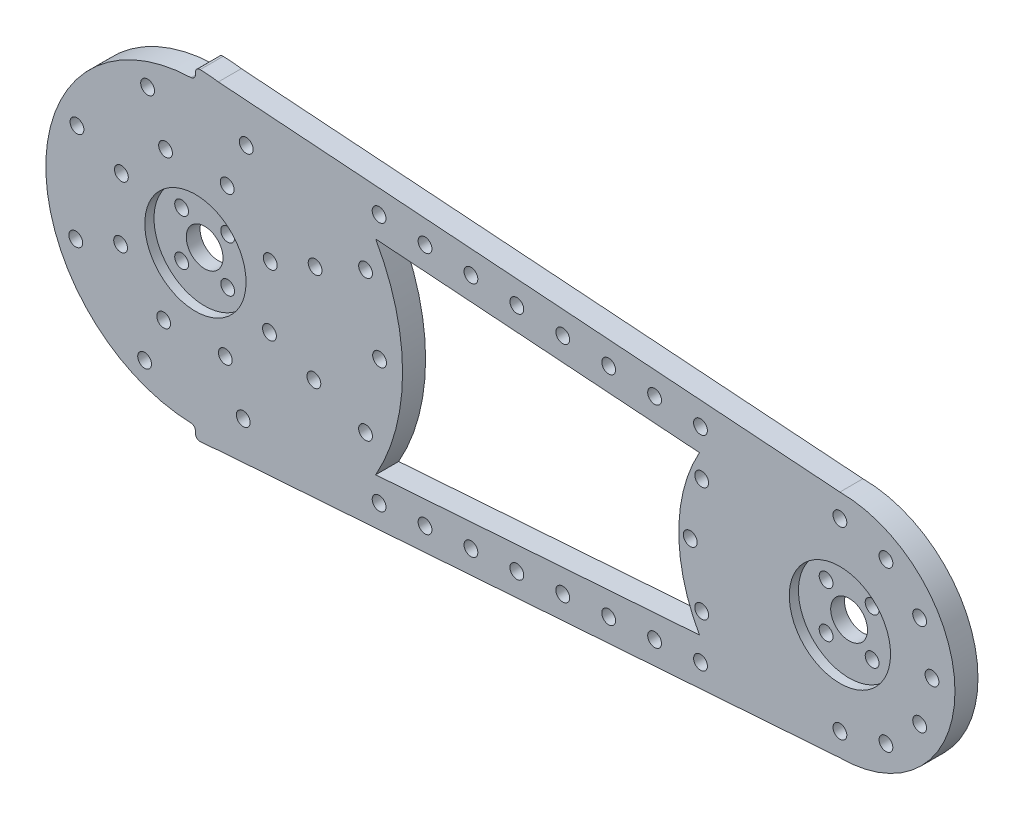
SolidWorks part; units mm, degrees
ref_plane "前视基准面" through (0, 0, 0) normal (0, 0, 1) x (1, 0, 0)
ref_plane "上视基准面" through (0, 0, 0) normal (0, 1, 0) x (1, 0, 0)
ref_plane "右视基准面" through (0, 0, 0) normal (1, 0, 0) x (0, 0, -1)
other "Configuration Table"
sketch "草图1" plane through (0, 0, 0) normal (0, 0, 1) x (1, 0, 0)
  line L0 (0, 0) -> (140, 0)
  line L1 (0, 35) -> (140, 25)
  line L2 (0, -35) -> (140, -25)
  circle A0 centre (0, 0) radius 35
  circle A1 centre (140, 0) radius 25
  dimension "D1" = 70
  dimension "D3" = 50
  dimension "D2" = 140
extrude "凸台-拉伸3" add sketch "草图1" along normal blind 5
sketch "草图4" plane through (0, 0, 5) normal (0, 0, 1) x (1, 0, 0)
  line L1 (-5, -5) -> (5, -5)
  line L2 (-5, -5) -> (-5, 5)
  line L3 (-5, 5) -> (5, 5)
  line L4 (5, -5) -> (5, 5)
  line L5 (-5, -5) -> (5, 5) construction
  line L6 (-5, 5) -> (5, -5) construction
  line L7 (135, -5) -> (145, -5)
  line L8 (135, -5) -> (135, 5)
  line L9 (135, 5) -> (145, 5)
  line L10 (145, -5) -> (145, 5)
  line L11 (135, -5) -> (145, 5) construction
  line L12 (135, 5) -> (145, -5) construction
  circle A0 centre (0, 0) radius 4
  circle A1 centre (-5, 5) radius 1.5
  circle A2 centre (5, 5) radius 1.5
  circle A3 centre (5, -5) radius 1.5
  circle A4 centre (-5, -5) radius 1.5
  circle A5 centre (140, 0) radius 4
  circle A6 centre (135, 5) radius 1.5
  circle A7 centre (145, 5) radius 1.5
  circle A8 centre (145, -5) radius 1.5
  circle A9 centre (135, -5) radius 1.5
  dimension "D1" = 8
  dimension "D4" = 3
  dimension "D6" = 8
  dimension "D9" = 3
  dimension "D2" = 10
  dimension "D3" = 10
  dimension "D7" = 10
  dimension "D8" = 10
  dimension "D5" = 4
  dimension "D10" = 4
extrude "切除-拉伸3" cut sketch "草图4" against normal blind 5 contours A5 | A0 | L2 A4 L1 | L1 A4 L2 | A6 | A9 | A8 | A7 | A1 | A2 | A3
sketch "草图5" plane through (0, 0, 5) normal (0, 0, 1) x (1, 0, 0)
  circle A0 centre (0, 0) radius 11
  circle A1 centre (140, 0) radius 11
  dimension "D1" = 22
  dimension "D2" = 22
extrude "切除-拉伸4" cut sketch "草图5" against normal blind 2
sketch "草图6" plane through (0, 0, 5) normal (0, 0, 1) x (1, 0, 0)
  circle A0 centre (0, 0) radius 30
  circle A1 centre (0, 30) radius 1.5
  circle A2 centre (15, 25.9808) radius 1.5
  circle A3 centre (25.9808, 15) radius 1.5
  circle A4 centre (30, 0) radius 1.5
  circle A5 centre (25.9808, -15) radius 1.5
  circle A6 centre (15, -25.9808) radius 1.5
  circle A7 centre (0, -30) radius 1.5
  circle A8 centre (-15, -25.9808) radius 1.5
  circle A9 centre (-25.9808, -15) radius 1.5
  circle A10 centre (-30, 0) radius 1.5
  circle A11 centre (-25.9808, 15) radius 1.5
  circle A12 centre (-15, 25.9808) radius 1.5
  circle A13 centre (140, 0) radius 20
  circle A14 centre (140, 20) radius 1.5
  circle A15 centre (150, 17.3205) radius 1.5
  circle A16 centre (157.3205, 10) radius 1.5
  circle A17 centre (160, 0) radius 1.5
  circle A18 centre (157.3205, -10) radius 1.5
  circle A19 centre (150, -17.3205) radius 1.5
  circle A20 centre (140, -20) radius 1.5
  circle A21 centre (130, -17.3205) radius 1.5
  circle A22 centre (122.6795, -10) radius 1.5
  circle A23 centre (120, 0) radius 1.5
  circle A24 centre (122.6795, 10) radius 1.5
  circle A25 centre (130, 17.3205) radius 1.5
  point P29 (0, 0)
  dimension "D1" = 60
  dimension "D2" = 3
  dimension "D4" = 40
  dimension "D5" = 3
  dimension "D3" = 12
  dimension "D6" = 12
extrude "切除-拉伸6" cut sketch "草图6" against normal through all contours A0 A12 | A11 | A1 | A2 | A3 | A4 | A5 | A6 | A7 | A8 | A9 | A10 | A25 | A14 | A15 | A16 | A17 | A18 | A19 | A20 | A21 | A22 | A23 | A24
sketch "草图8" plane through (0, 0, 5) normal (0, 0, 1) x (1, 0, 0)
  line L4 (-0.1715, -29.9995) -> (139.8316, -19.9993)
  line L5 (139.8316, 19.9993) -> (-0.1715, 29.9995)
  line L6 (-0.1715, -29.9995) -> (139.8316, -19.9993)
  line L7 (139.8316, 19.9993) -> (-0.1715, 29.9995)
  line L8 (-0.7125, 25.0254) -> (139.2875, 15.0254)
  line L9 (-0.7125, 25.0254) -> (139.2875, 15.0254)
  line L11 (-0.7125, -25.0254) -> (139.2875, -15.0254)
  line L12 (-0.7125, -25.0254) -> (139.2875, -15.0254)
  circle A3 centre (0, 30) radius 1.5
  arc A4 (139.8316, -19.9993) -> (139.8316, 19.9993) centre (140, 0) ccw
  arc A5 (-0.1715, 29.9995) -> (-0.1715, -29.9995) centre (0, 0) ccw
  arc A6 (139.8316, -19.9993) -> (139.8316, 19.9993) centre (140, 0) ccw
  arc A7 (-0.1715, 29.9995) -> (-0.1715, -29.9995) centre (0, 0) ccw
  circle A8 centre (9.9746, 29.2875) radius 1.5
  circle A9 centre (19.9492, 28.5751) radius 1.5
  circle A10 centre (29.9238, 27.8626) radius 1.5
  circle A11 centre (39.8983, 27.1501) radius 1.5
  circle A12 centre (49.8729, 26.4376) radius 1.5
  circle A13 centre (59.8475, 25.7252) radius 1.5
  circle A14 centre (69.8221, 25.0127) radius 1.5
  circle A15 centre (79.7967, 24.3002) radius 1.5
  circle A16 centre (89.7713, 23.5878) radius 1.5
  circle A17 centre (99.7459, 22.8753) radius 1.5
  circle A18 centre (109.7205, 22.1628) radius 1.5
  circle A19 centre (119.695, 21.4504) radius 1.5
  circle A20 centre (129.6696, 20.7379) radius 1.5
  circle A21 centre (0, -30) radius 1.5
  circle A22 centre (9.9746, -29.2875) radius 1.5
  circle A23 centre (19.9492, -28.5751) radius 1.5
  circle A24 centre (29.9238, -27.8626) radius 1.5
  circle A25 centre (39.8983, -27.1501) radius 1.5
  circle A26 centre (49.8729, -26.4376) radius 1.5
  circle A27 centre (59.8475, -25.7252) radius 1.5
  circle A28 centre (69.8221, -25.0127) radius 1.5
  circle A29 centre (79.7967, -24.3002) radius 1.5
  circle A30 centre (89.7713, -23.5878) radius 1.5
  circle A31 centre (99.7459, -22.8753) radius 1.5
  circle A32 centre (109.7205, -22.1628) radius 1.5
  circle A33 centre (119.695, -21.4504) radius 1.5
  circle A34 centre (129.6696, -20.7379) radius 1.5
  circle A35 centre (0, 0) radius 35
  circle A36 centre (140, 0) radius 25
  dimension "D2" = 14
  dimension "D1" = 5
  dimension "D4" = 10
  dimension "D5" = 10
  dimension "D3" = 14
extrude "切除-拉伸8" cut sketch "草图8" against normal through all contours A36 L9 A35 L12 | L6 A25 | L6 A25 | A8 | A9 | A10 | A11 | A12 | A13 | A14 | A16 | A15 | A17 | A18 | A19 | A20 | A34 | A33 | A32 | A31 | A30 | A29 | A28 | A27 | A26 | A24 | A23 | A22
sketch "草图9" plane through (0, 0, 5) normal (0, 0, 1) x (1, 0, 0)
  circle A0 centre (15, 25.9808) radius 1.5
  circle A1 centre (15, -25.9808) radius 1.5
extrude "凸台-拉伸4" add sketch "草图9" against normal blind 5
sketch "草图10" plane through (0, 0, 5) normal (0, 0, 1) x (1, 0, 0)
  circle A0 centre (130, -17.3205) radius 1.5
  circle A1 centre (130, 17.3205) radius 1.5
extrude "凸台-拉伸6" add sketch "草图10" against normal blind 5
sketch "草图11" plane through (0, 0, 5) normal (0, 0, 1) x (1, 0, 0)
  circle A0 centre (25.9808, -15) radius 1.5
  circle A1 centre (30, 0) radius 1.5
  circle A2 centre (25.9808, 15) radius 1.5
  circle A3 centre (122.6795, -10) radius 1.5
  circle A4 centre (120, 0) radius 1.5
  circle A5 centre (122.6795, 10) radius 1.5
  circle A6 centre (119.695, 21.4504) radius 1.5
  circle A7 centre (119.695, -21.4504) radius 1.5
  circle A8 centre (29.9238, -27.8626) radius 1.5
  circle A9 centre (29.9238, 27.8626) radius 1.5
  circle A10 centre (0, 0) radius 11
  circle A11 centre (0, 0) radius 35
  circle A12 centre (19.9492, -28.5751) radius 1.5
  circle A13 centre (19.9492, 28.5751) radius 1.5
  circle A14 centre (140, 0) radius 11
  circle A15 centre (140, 0) radius 24.9365
  circle A16 centre (129.6696, -20.7379) radius 1.5
  circle A17 centre (129.6696, 20.7379) radius 1.5
extrude "凸台-拉伸12" add sketch "草图11" against normal blind 5 contours A16 | A7 | A6 | A13 A11 A12 A0 A1 A2 A10 | A1 | A2 | A11 A13 | A11 A13 | A9 | A8 | A17
sketch "草图14" plane through (0, 0, 0) normal (0, 0, -1) x (-1, 0, 0)
  circle A2 centre (-11.0396, 25.7318) radius 1.5
  circle A3 centre (-6.8997, 16.0824) radius 1.5
  circle A4 centre (6.4931, 16.2508) radius 1.5
  circle A5 centre (10.389, 26.0013) radius 1.5
  circle A6 centre (16.0824, 6.8997) radius 1.5
  circle A7 centre (25.7318, 11.0396) radius 1.5
  circle A8 centre (16.2508, -6.4931) radius 1.5
  circle A9 centre (26.0013, -10.389) radius 1.5
  circle A10 centre (6.8997, -16.0824) radius 1.5
  circle A11 centre (11.0396, -25.7318) radius 1.5
  circle A12 centre (-6.4931, -16.2508) radius 1.5
  circle A13 centre (-10.389, -26.0013) radius 1.5
  circle A14 centre (-16.0824, -6.8997) radius 1.5
  circle A15 centre (-25.7318, -11.0396) radius 1.5
  circle A16 centre (-16.2508, 6.4931) radius 1.5
  circle A17 centre (-26.0013, 10.389) radius 1.5
  point P41 (0, 0)
  dimension "D1" = 8
extrude "切除-拉伸9" cut sketch "草图14" against normal blind 5
sketch "草图15" plane through (0, 0, 0) normal (0, 0, -1) x (-1, 0, 0)
  line L0 (-26.2977, -23.0961) -> (-32.9913, -22.618)
  line L1 (-26.2977, -23.0961) -> (-121.0676, -16.3268) construction
  line L2 (-26.2977, 23.0961) -> (-32.9913, 22.618)
  line L3 (-26.2977, 23.0961) -> (-121.0676, 16.3268) construction
  circle A0 centre (0, 0) radius 35
  circle A1 centre (0, 0) radius 40
  dimension "D1" = 80
extrude "凸台-拉伸13" add sketch "草图15" against normal blind 5 contours L2 A1 L0 A0
sketch "草图16" plane through (0, 0, 0) normal (0, 0, -1) x (-1, 0, 0)
  circle A1 centre (-35, 0) radius 1.5
  circle A2 centre (-32.3358, 13.3939) radius 1.5
  circle A16 centre (-32.3358, -13.3939) radius 1.5
  circle A17 centre (-24.7487, 24.7487) radius 1.5
  circle A18 centre (-24.7487, -24.7487) radius 1.5
  circle A19 centre (-13.3939, -32.3358) radius 1.5
  circle A20 centre (-13.3939, 32.3358) radius 1.5
  circle A21 centre (0, 35) radius 1.5
  circle A22 centre (13.3939, 32.3358) radius 1.5
  circle A23 centre (24.7487, 24.7487) radius 1.5
  circle A24 centre (32.3358, 13.3939) radius 1.5
  circle A25 centre (35, 0) radius 1.5
  circle A26 centre (32.3358, -13.3939) radius 1.5
  circle A27 centre (24.7487, -24.7487) radius 1.5
  circle A28 centre (13.3939, -32.3358) radius 1.5
  circle A29 centre (0, -35) radius 1.5
  dimension "D1" = 3
  dimension "D2" = 16
extrude "切除-拉伸10" cut sketch "草图16" against normal blind 5
sketch "草图18" plane through (0, 0, 5) normal (0, 0, 1) x (1, 0, 0)
  line L0 (32.9913, 22.618) -> (39.1555, 22.1777)
  line L1 (32.9913, 22.618) -> (121.0676, 16.3268) construction
  line L2 (32.9913, -22.618) -> (39.1555, -22.1777)
  line L3 (32.9913, -22.618) -> (121.0676, -16.3268) construction
  circle A0 centre (0, 0) radius 40
  circle A1 centre (0, 0) radius 45
  dimension "D1" = 90
extrude "凸台-拉伸14" add sketch "草图18" against normal blind 5 contours L2 A1 L0 A0
sketch "草图19" plane through (0, 0, 5) normal (0, 0, 1) x (1, 0, 0)
  circle A0 centre (32.3358, 13.3939) radius 1.5
  circle A1 centre (35, 0) radius 1.5
  circle A2 centre (32.3358, -13.3939) radius 1.5
extrude "凸台-拉伸15" add sketch "草图19" against normal blind 5
sketch "草图20" plane through (0, 0, 0) normal (0, 0, -1) x (-1, 0, 0)
  circle A1 centre (-40, 0) radius 1.5
  circle A2 centre (-36.9552, 15.3073) radius 1.5
  circle A4 centre (-15.3073, 36.9552) radius 1.5
  circle A5 centre (0, 40) radius 1.5
  circle A6 centre (15.3073, 36.9552) radius 1.5
  circle A7 centre (28.2843, 28.2843) radius 1.5
  circle A8 centre (36.9552, 15.3073) radius 1.5
  circle A9 centre (40, 0) radius 1.5
  circle A10 centre (36.9552, -15.3073) radius 1.5
  circle A11 centre (28.2843, -28.2843) radius 1.5
  circle A12 centre (15.3073, -36.9552) radius 1.5
  circle A13 centre (0, -40) radius 1.5
  circle A14 centre (-15.3073, -36.9552) radius 1.5
  circle A16 centre (-36.9552, -15.3073) radius 1.5
  circle A17 centre (-28.2843, -28.2843) radius 1.5
  circle A18 centre (-28.2843, 28.2843) radius 1.5
  point P38 (0, 0)
  dimension "D2" = 3
  dimension "D3" = 16
extrude "切除-拉伸11" cut sketch "草图20" against normal blind 5
sketch "草图21" plane through (0, 0, 0) normal (0, 0, -1) x (-1, 0, 0)
  line L0 (-121.0676, 16.3268) -> (-115.113, 16.7522)
  line L1 (-39.1555, 22.1777) -> (-121.0676, 16.3268) construction
  line L2 (-121.0676, -16.3268) -> (-115.113, -16.7522)
  line L3 (-39.1555, -22.1777) -> (-121.0676, -16.3268) construction
  circle A0 centre (-140, 0) radius 25
  circle A1 centre (-140, 0) radius 27.5
  circle A2 centre (-140, 0) radius 30
  dimension "D1" = 50
  dimension "D2" = 55
  dimension "D3" = 60
extrude "凸台-拉伸16" add sketch "草图21" against normal blind 5 contours L2 A1 L0 A0 | L2 A2 L0 A1
sketch "草图22" plane through (0, 0, 5) normal (0, 0, 1) x (1, 0, 0)
  circle A1 centre (122.6795, 10) radius 1.5
  circle A2 centre (120, 0) radius 1.5
  circle A3 centre (122.6795, -10) radius 1.5
extrude "凸台-拉伸17" add sketch "草图22" against normal blind 5
sketch "草图23" plane through (0, 0, 5) normal (0, 0, 1) x (1, 0, 0)
  circle A0 centre (140, 0) radius 27.5
  circle A1 centre (112.5, 0) radius 1.5
  circle A2 centre (116.1843, 13.75) radius 1.5
  circle A4 centre (140, 27.5) radius 1.5
  circle A5 centre (153.75, 23.8157) radius 1.5
  circle A6 centre (163.8157, 13.75) radius 1.5
  circle A7 centre (167.5, 0) radius 1.5
  circle A8 centre (163.8157, -13.75) radius 1.5
  circle A9 centre (153.75, -23.8157) radius 1.5
  circle A10 centre (140, -27.5) radius 1.5
  circle A12 centre (116.1843, -13.75) radius 1.5
  circle A13 centre (126.25, 23.8157) radius 1.5
  circle A14 centre (126.25, -23.8157) radius 1.5
  dimension "D1" = 55
  dimension "D2" = 3
  dimension "D3" = 12
extrude "切除-拉伸15" cut sketch "草图23" against normal blind 5 contours A0 A2 | A0 A12 | A0 A12 | A1
sketch "草图24" plane through (0, 0, 5) normal (0, 0, 1) x (1, 0, 0)
  circle A0 centre (116.1843, 13.75) radius 1.5
  circle A1 centre (112.5, 0) radius 1.5
  circle A2 centre (116.1843, -13.75) radius 1.5
extrude "凸台-拉伸21" add sketch "草图24" against normal blind 5
sketch "草图29" plane through (0, 0, 5) normal (0, 0, 1) x (1, 0, 0)
  line L0 (115.113, 16.7522) -> (109.4918, 17.1537)
  line L1 (39.1555, 22.1777) -> (115.113, 16.7522) construction
  line L2 (115.113, -16.7522) -> (109.4918, -17.1537)
  line L3 (39.1555, -22.1777) -> (115.113, -16.7522) construction
  circle A0 centre (140, 0) radius 35
  circle A1 centre (140, 0) radius 30
  circle A2 centre (140, 0) radius 32.5
  circle A3 centre (107.5, 0) radius 1.5
  circle A4 centre (109.9739, 12.4372) radius 1.5
  circle A5 centre (117.019, 22.981) radius 1.5
  circle A6 centre (127.5628, 30.0261) radius 1.5
  circle A7 centre (140, 32.5) radius 1.5
  circle A8 centre (152.4372, 30.0261) radius 1.5
  circle A9 centre (162.981, 22.981) radius 1.5
  circle A10 centre (170.0261, 12.4372) radius 1.5
  circle A11 centre (172.5, 0) radius 1.5
  circle A12 centre (170.0261, -12.4372) radius 1.5
  circle A13 centre (162.981, -22.981) radius 1.5
  circle A14 centre (152.4372, -30.0261) radius 1.5
  circle A15 centre (140, -32.5) radius 1.5
  circle A16 centre (127.5628, -30.0261) radius 1.5
  circle A17 centre (117.019, -22.981) radius 1.5
  circle A18 centre (109.9739, -12.4372) radius 1.5
  dimension "D1" = 70
  dimension "D2" = 65
  dimension "D3" = 3
  dimension "D4" = 16
extrude "凸台-拉伸22" add sketch "草图29" against normal blind 5 contours A18 A2 L2 A1 L0 A4 A3 | A18 A2 A3 A4 L0 A0 L2
sketch "草图30" plane through (0, 0, 0) normal (0, 0, -1) x (-1, 0, 0)
  line L0 (0, 0) -> (0, 35)
  line L1 (0, 35) -> (0, -35)
  circle A0 centre (0, 0) radius 35
  circle A1 centre (0, 0) radius 32.5
  dimension "D1" = 65
extrude "切除-拉伸16" cut sketch "草图30" against normal blind 10 contours A1 L1 A0
fillet "圆角5" radius 1 1 edges at (0, 35, 2.5)
fillet "圆角6" radius 1 1 edges at (0, -35, 2.5)
fillet "圆角7" radius 1 1 edges at (0, -32.5, 2.5)
fillet "圆角8" radius 1 1 edges at (0, 32.5, 2.5)
